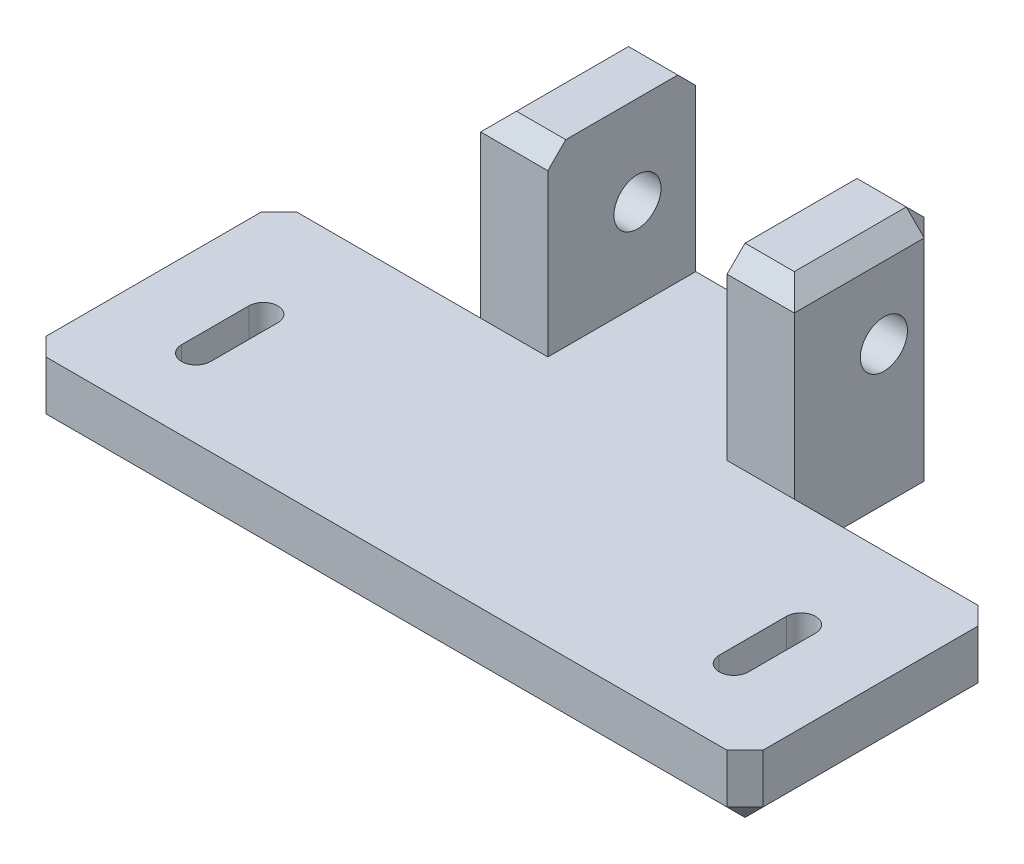
SolidWorks part; units mm, degrees
ref_plane "Front Plane" through (0, 0, 0) normal (0, 0, 1) x (1, 0, 0)
ref_plane "Top Plane" through (0, 0, 0) normal (0, 1, 0) x (1, 0, 0)
ref_plane "Right Plane" through (0, 0, 0) normal (1, 0, 0) x (0, 0, -1)
sketch "Sketch1" plane through (0, 0, 0) normal (1, 0, 0) x (0, 0, -1)
  line L0 (-10, -10) -> (6.5, -10)
  line L5 (-10, 10) -> (6.5, 10)
  line L7 (-10, -17.5) -> (6.5, -17.5)
  line L8 (6.5, 10) -> (6.5, -17.5)
  line L9 (-10, -10) -> (-38, -10)
  line L10 (-38, -10) -> (-38, -17.5)
  line L11 (-38, -17.5) -> (-10, -17.5)
  line L12 (6.5, 10) -> (10, 10) construction
  line L13 (10, 10) -> (10, -17.5) construction
  line L14 (10, -17.5) -> (6.5, -17.5) construction
  line L15 (-10, -10) -> (-10, 10)
  line L16 (-10, -17.5) -> (-10, -10)
  line L17 (-13, -10) -> (-13, -17.5) construction
  line L18 (-25.5, -10) -> (-25.5, -17.5) construction
  circle A0 centre (0, 0) radius 2.625
  point P4 (-10, 0)
  point P6 (0, 0)
  dimension "D9" = 5.25
  dimension "D1" = 20
  dimension "D2" = 10
  dimension "D3" = 20
  dimension "D4" = 7.5
  dimension "D5" = 3.5
  dimension "D6" = 3
  dimension "D7" = 25
  dimension "D8" = 12.5
extrude "Boss-Extrude1" add sketch "Sketch1" along normal blind 7.5 from offset 10 contours L15 L0 L8 L5 region at (0, 0, 9.7407)
extrude "Boss-Extrude2" add sketch "Sketch1<3>" against normal blind 7.5 from offset 10 separate body contours L15 L0 L8 L5 region at (0, 0, 9.7407) offset against normal yes
sketch "Sketch1<3>" plane through (0, 0, 0) normal (1, 0, 0) x (0, 0, -1) same geometry as "Sketch1"
extrude "Boss-Extrude3" add sketch "Sketch1<4>" along normal up to surface (17.5 mm away) and the other way up to surface (17.5 mm away) contours L16 L7 L8 L0 | L11 L16 L9 L10 region at (0, -13.75, 24) region at (0, -13.75, 1.75) up to face at (17.5, 0, -2.625) other way up to face at (-17.5, 0, -2.625)
sketch "Sketch1<4>" plane through (0, 0, 0) normal (1, 0, 0) x (0, 0, -1) same geometry as "Sketch1"
sketch "Sketch2" plane through (0, -10, 0) normal (0, 1, 0) x (1, 0, 0)
  line L0 (-17.5, -10) -> (-40, -10)
  line L1 (-40, -10) -> (-40, -38)
  line L2 (-40, -38) -> (-17.5, -38)
  line L3 (-17.5, -10) -> (-17.5, -38)
  line L4 (0, -1000) -> (0, 49000) construction
  line L5 (17.5, -10) -> (17.5, -38)
  line L6 (40, -38) -> (17.5, -38)
  line L7 (40, -10) -> (40, -38)
  line L8 (17.5, -10) -> (40, -10)
  line L9 (-30, -29.25) -> (-30, -21.75) construction
  line L10 (-31.625, -29.25) -> (-31.625, -21.75)
  line L11 (-28.375, -29.25) -> (-28.375, -21.75)
  line L12 (30, -29.25) -> (30, -21.75) construction
  line L13 (31.625, -29.25) -> (31.625, -21.75)
  line L14 (28.375, -29.25) -> (28.375, -21.75)
  arc A0 (-31.625, -29.25) -> (-28.375, -29.25) centre (-30, -29.25) ccw
  arc A1 (-28.375, -21.75) -> (-31.625, -21.75) centre (-30, -21.75) ccw
  arc A2 (31.625, -29.25) -> (28.375, -29.25) centre (30, -29.25) cw
  arc A3 (28.375, -21.75) -> (31.625, -21.75) centre (30, -21.75) cw
  point P6 (-30, -25.5)
  point P13 (30, -25.5)
  point P14 (-30, -25.5)
  point P24 (30, -25.5)
  line M6 (-17.5, -10) -> (-17.5, -38)
  line M8 (17.5, -38) -> (17.5, -10)
  dimension "D4" = 1.625
  dimension "D1" = 12.5
  dimension "D2" = 60
  dimension "D3" = 10
  dimension "D5" = 7.5
extrude "Boss-Extrude4" add sketch "Sketch2" against normal up to surface (7.5 mm away) contours L1 L2 L0 M6 | L8 L6 L7 M8 region at (-17.8592, -10, 24) region at (28.75, -10, 10.3592) up to face at (0, -17.5, 15.75)
chamfer "Chamfer1" distance 2 angle 45 20 edges at (-13.75, 10, 10) (-17.5, 10, 1.75) (13.75, 10, 10) (17.5, 10, 1.75) (-13.75, 10, -6.5) (13.75, 10, -6.5) (-17.5, -3.75, -6.5) (17.5, -3.75, -6.5) (17.5, -17.5, 1.75) (28.75, -17.5, 10) (0, -17.5, -6.5) (-17.5, -17.5, 1.75) (-28.75, -17.5, 10) (-40, -17.5, 24) (40, -13.75, 10) (40, -17.5, 24) (40, -13.75, 38) (0, -17.5, 38) (-40, -13.75, 38) (-40, -13.75, 10)
equation "\"D8@Sketch1\"=\"D7@Sketch1\"/2"
